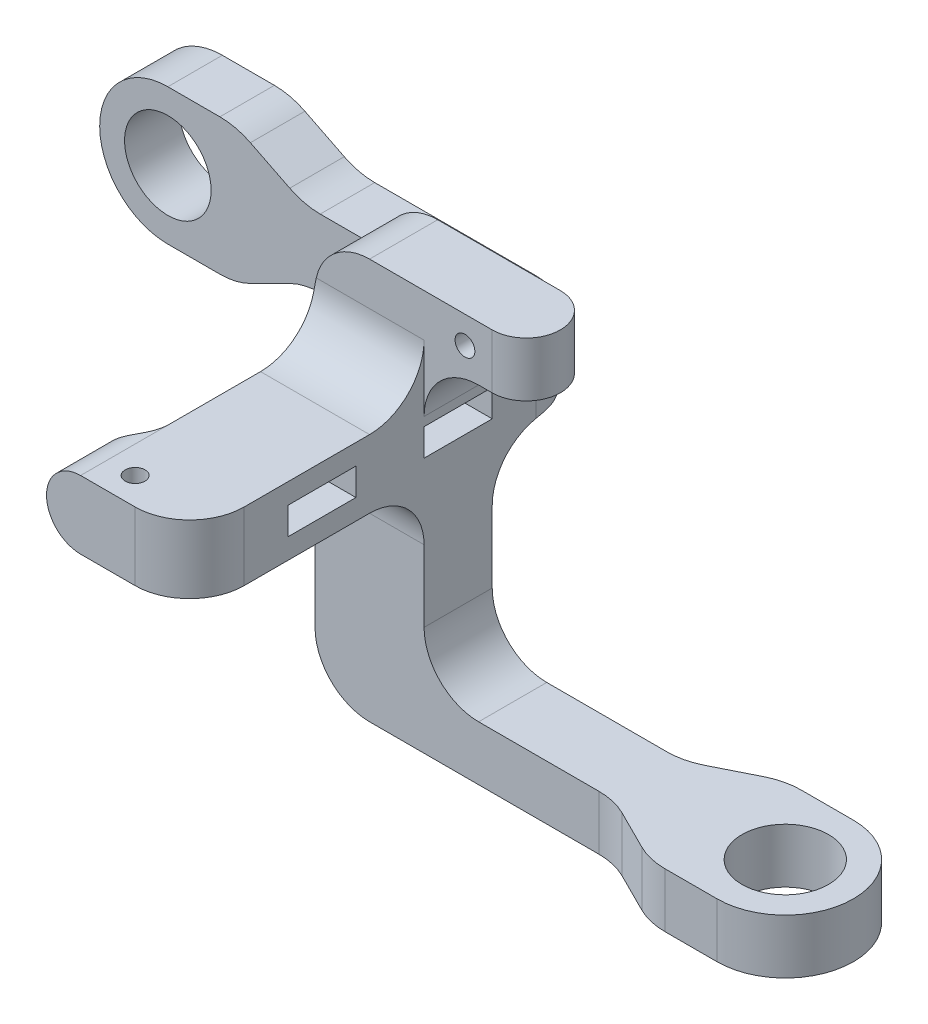
SolidWorks part; units mm, degrees
ref_plane "Face" through (0, 0, 0) normal (0, 0, 1) x (1, 0, 0)
ref_plane "Dessus" through (0, 0, 0) normal (0, 1, 0) x (1, 0, 0)
ref_plane "Droite" through (0, 0, 0) normal (1, 0, 0) x (0, 0, -1)
sketch "Sketch1" plane through (0, 0, 0) normal (0, 0, 1) x (1, 0, 0)
  line L0 (-8, 5) -> (-8, -5)
  line L1 (-8, -5) -> (8, -5)
  line L2 (8, -5) -> (8, 5)
  line L3 (8, 5) -> (-8, 5)
  dimension "D1" = 10
  dimension "D2" = 16
  dimension "D3" = 8
  dimension "D4" = 5
extrude "Boss-Extrude1" add sketch "Sketch1" along normal blind 58.8
ref_plane "Plane1" through (0, 0, 58.8) normal (0, 0, 1) x (1, 0, 0)
sketch "Sketch2" plane through (0, 0, 58.8) normal (0, 0, 1) x (1, 0, 0)
  line L0 (-8, 5) -> (-8, -5)
  arc A0 (-8, 5) -> (-8, -5) centre (-8, 0) ccw
extrude "Boss-Extrude2" add sketch "Sketch2" against normal blind 8
sketch "Sketch4" plane through (0, 0, 0) normal (0, 0, 1) x (1, 0, 0)
  line L0 (-8, 5) -> (-8, -5)
  line L1 (-8, -5) -> (-26, -5)
  line L2 (-26, -5) -> (-36, -10)
  line L3 (-36, -10) -> (-46, -10)
  line L4 (-46, 10) -> (-36, 10)
  line L5 (-36, 10) -> (-26, 5)
  line L6 (-26, 5) -> (-8, 5)
  line L8 (0, 5) -> (0, -5) construction
  line L9 (8, 5) -> (-8, 5) construction
  line L10 (-8, -5) -> (8, -5) construction
  arc A0 (-46, -10) -> (-46, 10) centre (-46, 0) cw
  circle A1 centre (-46, 0) radius 6.35
  dimension "D1" = 10
  dimension "D8" = 12.7
  dimension "D2" = 38
  dimension "D3" = 5
  dimension "D4" = 10
  dimension "D5" = 10
  dimension "D6" = 10
  dimension "D7" = 10
extrude "Boss-Extrude4" add sketch "Sketch4" along normal blind 8
sketch "Sketch7" plane through (0, -5, 0) normal (0, -1, 0) x (1, 0, 0)
  line L0 (-8, 58.8) -> (8, 58.8) construction
  circle A0 centre (-4, 54.8) radius 1.45
  dimension "D1" = 4
  dimension "D3" = 2.9
  dimension "D2" = 4
extrude "Cut-Extrude1" cut sketch "Sketch7" against normal through all
ref_plane "Plane2" through (0, 0, 14.4) normal (0, 0, 1) x (1, 0, 0)
sketch "Sketch8" plane through (0, 0, 14.4) normal (0, 0, 1) x (1, 0, 0)
  line L0 (-8, 5) -> (-8, 19.3)
  line L1 (-8, 5) -> (8, 5)
  line L2 (8, 5) -> (8, 19.3)
  line L3 (8, 19.3) -> (-8, 19.3)
  line L4 (-8, -5) -> (8, -5)
  line L5 (8, -5) -> (8, -39.5)
  line L6 (8, -39.5) -> (-8, -39.5)
  line L7 (-8, -39.5) -> (-8, -5)
  dimension "D1" = 58.8
  dimension "D2" = 14.3
extrude "Boss-Extrude5" add sketch "Sketch8" along normal blind 10
sketch "Sketch9" plane through (0, -39.5, -40.5) normal (0, 1, 0) x (1, 0, 0)
  line L13 (36, -54.9) -> (8, -54.9)
  line L14 (46, -49.9) -> (36, -54.9)
  line L15 (56, -49.9) -> (46, -49.9)
  line L16 (46, -69.9) -> (56, -69.9)
  line L17 (36, -64.9) -> (46, -69.9)
  line L18 (8, -64.9) -> (36, -64.9)
  line L19 (8, -54.9) -> (8, -64.9)
  circle A2 centre (56, -59.9) radius 6.35
  arc A3 (56, -69.9) -> (56, -49.9) centre (56, -59.9) ccw
  dimension "D1" = 0
  dimension "D8" = 5
  dimension "D10" = 12.7
  dimension "D2" = 10
  dimension "D3" = 48
  dimension "D4" = 10
  dimension "D5" = 10
  dimension "D6" = 10
  dimension "D7" = 10
  dimension "D9" = 5
extrude "Boss-Extrude6" add sketch "Sketch9" along normal blind 8
sketch "Sketch10" plane through (0, 19.3, 0) normal (0, 1, 0) x (1, 0, 0)
  line L0 (8, -24.4) -> (8, -14.4)
  line L1 (8, -14.4) -> (18, -14.4)
  line L2 (8, -24.4) -> (18, -24.4)
  arc A0 (18, -14.4) -> (18, -24.4) centre (18, -19.4) cw
  dimension "D1" = 10
  dimension "D2" = 10
extrude "Boss-Extrude7" add sketch "Sketch10" against normal blind 8
sketch "Sketch12" plane through (0, 0, 14.4) normal (0, 0, -1) x (-1, 0, 0)
  circle A0 centre (-14, 15.3) radius 1.45
  dimension "D3" = 2.9
  dimension "D1" = 4
  dimension "D2" = 4
extrude "Cut-Extrude2" cut sketch "Sketch12" against normal through all
sketch "Sketch14" plane through (-8, 0, 0) normal (-1, 0, 0) x (0, 0, 1)
  line L0 (34.4, -2) -> (34.4, 2)
  line L1 (14.4, -2) -> (24.4, -2)
  line L2 (14.4, -2) -> (14.4, 2)
  line L3 (14.4, 2) -> (24.4, 2)
  line L4 (24.4, -2) -> (24.4, 2)
  line L5 (34.4, -2) -> (44.4, -2)
  line L6 (44.4, -2) -> (44.4, 2)
  line L7 (34.4, 2) -> (44.4, 2)
  dimension "D1" = 10
  dimension "D2" = 4
  dimension "D3" = 3
  dimension "D4" = 0
  dimension "D6" = 10
  dimension "D5" = 2
extrude "Cut-Extrude3" cut sketch "Sketch14" against normal through all
fillet "Fillet1" radius 8 4 edges at (-8, 19.3, 19.4) (8, 0, 0) (-8, -39.5, 19.4) (8, 0, 58.8)
fillet "Fillet2" radius 10 8 edges at (36, -35.5, 14.4) (46, -35.5, 9.4) (46, -35.5, 29.4) (36, -35.5, 24.4) (-36, -10, 4) (-26, -5, 4) (-26, 5, 4) (-36, 10, 4)
fillet "Fillet3" radius 8 3 edges at (-8, 0, 8) (8, -31.5, 19.4) (8, 11.3, 19.4)
fillet "Fillet4" radius 5 1 edges at (-8, 0, 50.8)
fillet "Fillet5" radius 8 4 edges at (0, 5, 14.4) (0, -5, 14.4) (0, -5, 24.4) (0, 5, 24.4)
